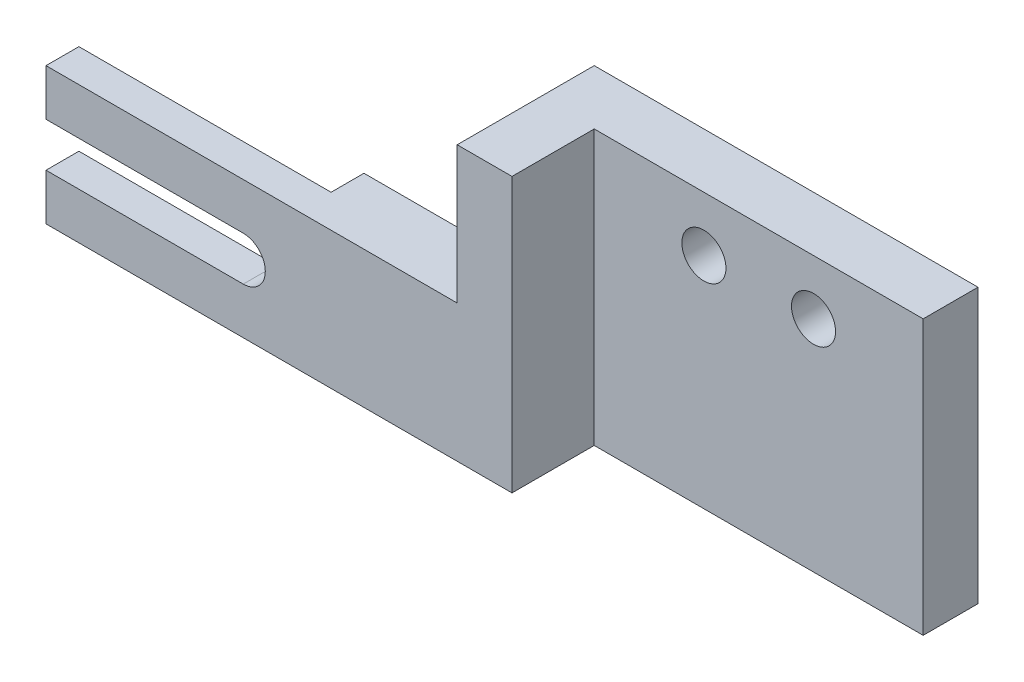
SolidWorks part; units mm, degrees
ref_plane "Front Plane" through (0, 0, 0) normal (0, 0, 1) x (1, 0, 0)
ref_plane "Top Plane" through (0, 0, 0) normal (0, 1, 0) x (1, 0, 0)
ref_plane "Right Plane" through (0, 0, 0) normal (1, 0, 0) x (0, 0, -1)
sketch "Sketch1" plane through (0, 0, 0) normal (0, 1, 0) x (1, 0, 0)
  line L1 (-46.0375, -7.9375) -> (46.0375, -7.9375)
  line L2 (-46.0375, -7.9375) -> (-46.0375, 7.9375)
  line L3 (-46.0375, 7.9375) -> (46.0375, 7.9375)
  line L4 (46.0375, -7.9375) -> (46.0375, 7.9375)
  line L5 (-46.0375, -7.9375) -> (46.0375, 7.9375) construction
  line L6 (-46.0375, 7.9375) -> (46.0375, -7.9375) construction
  point P0 (0, 0)
  dimension "D1" = 92.075
  dimension "D2" = 15.875
extrude "Boss-Extrude1" add sketch "Sketch1" along normal mid plane 31.75
sketch "Sketch2" plane through (0, 0, 7.9375) normal (0, 0, 1) x (1, 0, 0)
  line L0 (46.0375, 15.875) -> (46.0375, -15.875) construction
  line L1 (-46.0375, 15.875) -> (1.5875, 15.875)
  line L2 (-46.0375, 15.875) -> (-46.0375, 0)
  line L3 (-46.0375, 0) -> (1.5875, 0)
  line L4 (1.5875, 15.875) -> (1.5875, 0)
  dimension "D1" = 44.45
  dimension "D2" = 15.875
extrude "Cut-Extrude1" cut sketch "Sketch2" against normal through all
hole_wizard "#10 (0.1935) Diameter Hole1" positions "Sketch4" profile "Sketch3" hole size "#10" standard "ANSI Inch" end condition up to next
sketch "Sketch4" plane through (0, 0, 7.9375) normal (0, 0, 1) x (1, 0, 0)
  line L0 (46.0375, 15.875) -> (46.0375, -15.875) construction
  line L2 (-46.0375, 0) -> (1.5875, 0) construction
  point P0 (33.3375, 9.525)
  point P2 (20.6375, 9.525)
  dimension "D1" = 12.7
  dimension "D2" = 12.7
  dimension "D3" = 9.525
sketch "Sketch3" plane through (33.3375, 9.525, 7.9375) normal (1, 0, 0) x (0, -1, 0)
  line L0 (0, 0) -> (0, 15.875)
  line L1 (0, 15.875) -> (2.5527, 15.875)
  line L2 (2.5527, 15.875) -> (2.5527, 0)
  line L5 (2.5527, 0) -> (0, 0)
  line L11 (0, -6.35) -> (0, 107.95) construction
  dimension "Thru Hole Dia." = 5.1054
  dimension "Thru Hole Depth" = 15.875
hole_wizard "#10 (0.1935) Diameter Slot1" positions "Sketch6" profile "Sketch5" size "#10" standard "ANSI Inch" slot yes end condition up to next
sketch "Sketch6" plane through (0, 0, 7.9375) normal (0, 0, 1) x (1, 0, 0)
  line L0 (-58.7375, -7.9375) -> (-20.6375, -7.9375) construction
  line L1 (-46.0375, -15.875) -> (46.0375, -15.875) construction
  line L2 (-46.0375, 0) -> (-46.0375, -15.875) construction
  point P0 (-39.6875, -7.9375)
  dimension "D1" = 38.1
  dimension "D2" = 7.9375
  dimension "D3" = 25.4
sketch "Sketch5" plane through (-39.6875, -7.9375, 7.9375) normal (1, 0, 0) x (0, -1, 0)
  line L0 (0, 0) -> (0, 15.875)
  line L1 (0, 15.875) -> (2.5527, 15.875)
  line L2 (2.5527, 15.875) -> (2.5527, 0)
  line L5 (2.5527, 0) -> (0, 0)
  line L11 (0, -6.35) -> (0, 107.95) construction
  dimension "Thru Hole Dia." = 5.1054
  dimension "Thru Hole Depth" = 15.875
sketch "Sketch7" plane through (0, 0, 0) normal (0, 1, 0) x (1, 0, 0)
  line L0 (46.0375, -7.9375) -> (46.0375, 7.9375) construction
  line L1 (-46.0375, 7.9375) -> (1.5875, 7.9375)
  line L2 (-46.0375, 7.9375) -> (-46.0375, -4.1275)
  line L3 (-46.0375, -4.1275) -> (1.5875, -4.1275)
  line L4 (1.5875, 7.9375) -> (1.5875, -4.1275)
  line L5 (-46.0375, -7.9375) -> (1.5875, -7.9375) construction
  dimension "D1" = 3.81
  dimension "D2" = 44.45
extrude "Cut-Extrude2" cut sketch "Sketch7" against normal up to next
sketch "Sketch8" plane through (0, 15.875, 0) normal (0, 1, 0) x (1, 0, 0)
  line L0 (1.5875, 7.9375) -> (1.5875, -7.9375) construction
  line L1 (46.0375, -7.9375) -> (7.9375, -7.9375)
  line L2 (46.0375, -7.9375) -> (46.0375, 1.5875)
  line L3 (46.0375, 1.5875) -> (7.9375, 1.5875)
  line L4 (7.9375, -7.9375) -> (7.9375, 1.5875)
  line L5 (46.0375, 7.9375) -> (1.5875, 7.9375) construction
  dimension "D1" = 6.35
  dimension "D2" = 6.35
extrude "Cut-Extrude3" cut sketch "Sketch8" against normal up to next
sketch "Sketch9" plane through (0, 0, 4.1275) normal (0, 0, -1) x (-1, 0, 0)
  line L0 (46.0375, -15.875) -> (-1.5875, -15.875) construction
  line L1 (-1.5875, 0) -> (16.8275, 0)
  line L2 (-1.5875, 0) -> (-1.5875, -15.875)
  line L3 (-1.5875, -15.875) -> (16.8275, -15.875)
  line L4 (16.8275, 0) -> (16.8275, -15.875)
  line L5 (46.0375, -5.3848) -> (46.0375, 0) construction
  line L6 (-1.5875, -15.875) -> (-1.5875, 15.875) construction
  dimension "D1" = 29.21
extrude "Boss-Extrude2" add sketch "Sketch9" along normal blind 3.81
